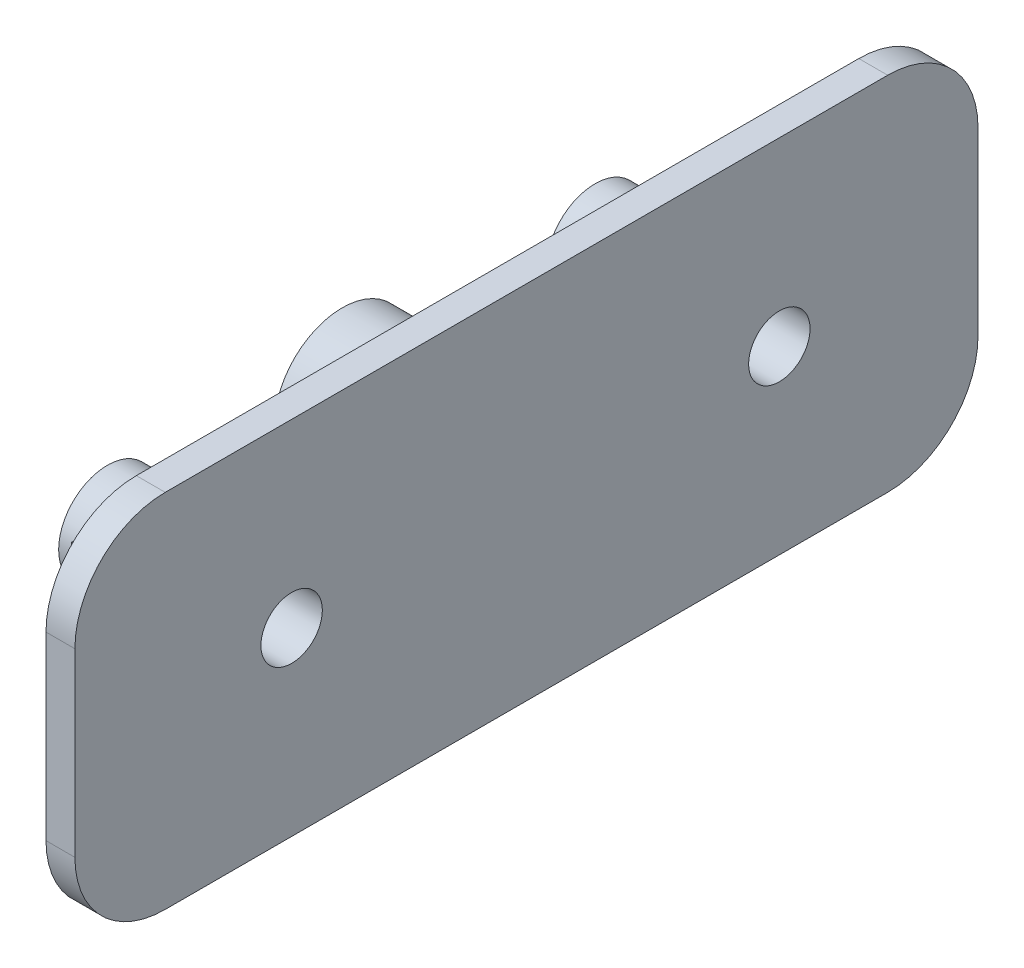
SolidWorks part; units mm, degrees
ref_plane "Front Plane" through (0, 0, 0) normal (0, 0, 1) x (1, 0, 0)
ref_plane "Top Plane" through (0, 0, 0) normal (0, 1, 0) x (1, 0, 0)
ref_plane "Right Plane" through (0, 0, 0) normal (1, 0, 0) x (0, 0, -1)
sketch "Sketch1" plane through (0, 0, 0) normal (1, 0, 0) x (0, 0, -1)
  circle A0 centre (0, 0) radius 2.5
  circle A2 centre (0, 0) radius 3.75
  dimension "D1" = 5
  dimension "D2" = 7.5
extrude "Boss-Extrude1" add sketch "Sketch1" along normal blind 5
sketch "Sketch2" plane through (5, 0, 0) normal (1, 0, 0) x (0, 0, -1)
  line L1 (-20, -5) -> (20, -5)
  line L2 (-20, -5) -> (-20, 5)
  line L3 (-20, 5) -> (20, 5)
  line L4 (20, -5) -> (20, 5)
  line L5 (-20, -5) -> (20, 5) construction
  line L6 (-20, 5) -> (20, -5) construction
  circle A0 centre (0, 0) radius 3
  point P0 (0, 0)
  dimension "D1" = 10
  dimension "D2" = 40
extrude "Boss-Extrude2" add sketch "Sketch2" along normal blind 3.6
sketch "Sketch7" plane through (8.6, 0, 0) normal (1, 0, 0) x (0, 0, -1)
  line L1 (25, -10) -> (-25, -10)
  line L2 (25, -10) -> (25, 10)
  line L3 (25, 10) -> (-25, 10)
  line L4 (-25, -10) -> (-25, 10)
  line L5 (25, -10) -> (-25, 10) construction
  line L6 (25, 10) -> (-25, -10) construction
  point P0 (0, 0)
  dimension "D1" = 50
  dimension "D2" = 20
extrude "Boss-Extrude3" add sketch "Sketch7" along normal blind 1.6
hole_wizard "M3 Clearance Hole1" positions "Sketch5" profile "Sketch6" hole size "M3" standard "ANSI Metric"
sketch "Sketch5" plane through (5, 0, 0) normal (-1, 0, 0) x (0, 0, 1)
  point P0 (-14, 0)
  point P2 (13, 0)
  dimension "D1" = 14
  dimension "D2" = 13
sketch "Sketch6" plane through (5, 0, -14) normal (0, 1, 0) x (0, 0, 1)
  line L0 (0, 0) -> (0, 13.0215)
  line L1 (0, 13.0215) -> (1.7, 12)
  line L2 (1.7, 12) -> (1.7, 0)
  line L5 (1.7, 0) -> (0, 0)
  line L10 (0, 13.0215) -> (-1.7, 12) construction
  line L11 (0, -6.35) -> (0, 107.95) construction
  dimension "Hole Dia." = 3.4
  dimension "Hole Depth" = 12
  dimension "Drill Angle" = 118
sketch "Sketch8" plane through (5, 0, 0) normal (-1, 0, 0) x (0, 0, 1)
  circle A0 centre (-14, 0) radius 1.7
  circle A1 centre (-14, 0) radius 2.7
  circle A2 centre (13, 0) radius 1.7
  circle A3 centre (13, 0) radius 2.7
  circle A4 centre (-14, 0) radius 1.7 construction
  circle A5 centre (13, 0) radius 1.7 construction
  dimension "D1" = 5.4
  dimension "D2" = 5.4
extrude "Boss-Extrude4" add sketch "Sketch8" along normal blind 5
fillet "Fillet2" radius 5 4 edges at (9.4, 10, -25) (9.4, -10, -25) (9.4, -10, 25) (9.4, 10, 25)
